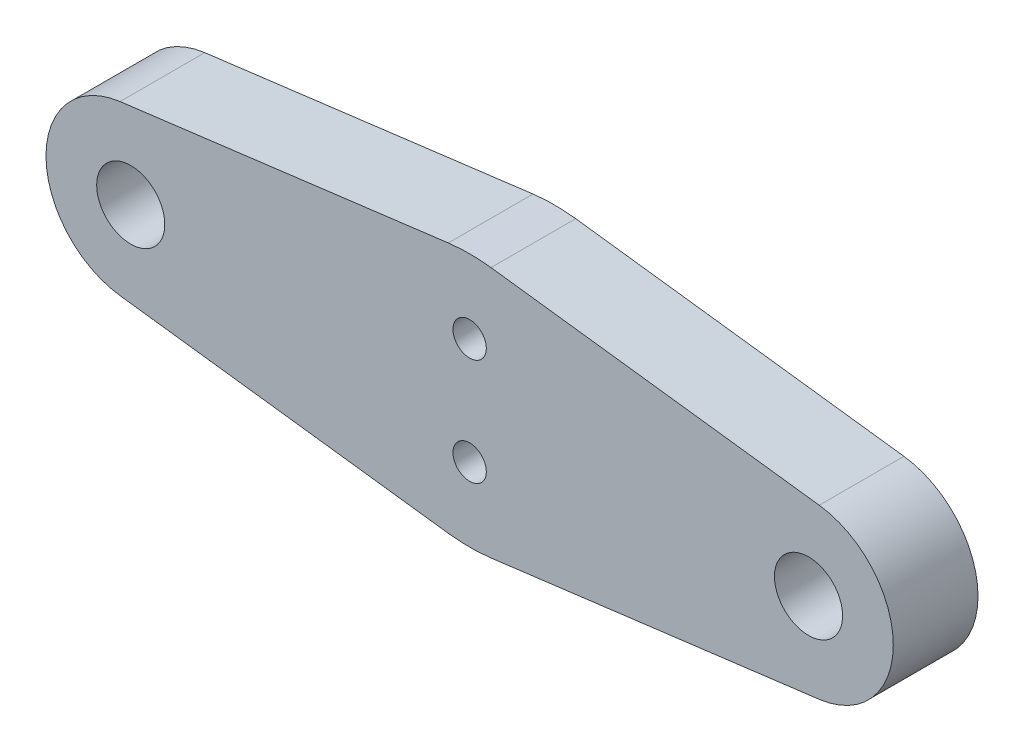
SolidWorks part; units mm, degrees
material "6061-T6 (SS)"
ref_plane "Front" through (0, 0, 0) normal (0, 0, 1) x (1, 0, 0)
ref_plane "Top" through (0, 0, 0) normal (0, 1, 0) x (1, 0, 0)
ref_plane "Right" through (0, 0, 0) normal (1, 0, 0) x (0, 0, -1)
sketch "Sketch1" plane through (0, 0, 0) normal (0, 0, 1) x (1, 0, 0)
  line L0 (1.6002, 9.4238) -> (26.2001, 6.2994)
  line L5 (26.2001, -6.2994) -> (1.6002, -9.4238)
  line L6 (-1.6002, 9.4238) -> (-26.2001, 6.2994)
  line L7 (-26.2001, -6.2994) -> (-1.6002, -9.4238)
  line L8 (25.4, 0) -> (-25.4, 0) construction
  line L9 (0, 3.175) -> (0, -3.175) construction
  arc A1 (26.2001, 6.2994) -> (26.2001, -6.2994) centre (25.4, 0) cw
  arc A2 (-26.2001, 6.2994) -> (-26.2001, -6.2994) centre (-25.4, 0) ccw
  arc A3 (1.6002, 9.4238) -> (-1.6002, 9.4238) centre (0, -3.175) ccw
  arc A4 (1.6002, -9.4238) -> (-1.6002, -9.4238) centre (0, 3.175) cw
  dimension "D1" = 12.7
  dimension "D2" = 6.35
  dimension "D4" = 19.05
  dimension "D3" = 50.8
extrude "Boss-Extrude1" add sketch "Sketch1" along normal blind 6.35
sketch "Sketch4" plane through (0, 0, 0) normal (0, 0, -1) x (-1, 0, 0)
  line L0 (0, 4) -> (0, -4) construction
  point P0 (0, 4)
  point P2 (0, -4)
  dimension "D1" = 8
hole_wizard "M3x0.5 Tapped Hole1" positions "Sketch4" profile "Sketch3" tap size "M3x0.5" standard "ANSI Metric" end condition up to next
sketch "Sketch3" plane through (0, 4, 0) normal (1, 0, 0) x (0, 1, 0)
  line L0 (0, 0) -> (0, 6.35)
  line L1 (0, 6.35) -> (1.25, 6.35)
  line L2 (1.25, 6.35) -> (1.25, 0)
  line L5 (1.25, 0) -> (0, 0)
  line L11 (0, -6.35) -> (0, 107.95) construction
  dimension "Thru Tap Drill Dia." = 2.5
  dimension "Thru Tap Drill Depth" = 6.35
cosmetic thread "Hole Thread1" parameters "D2"=3
cosmetic thread "Hole Thread2" parameters "D2"=3
sketch "Sketch7" plane through (0, 0, 0) normal (0, 0, -1) x (-1, 0, 0)
  point P11 (25.4, 0)
  point P14 (-25.4, 0)
hole_wizard "#10 Clearance Hole1" positions "Sketch7" profile "Sketch6" hole size "#10" standard "ANSI Inch" end condition through all
sketch "Sketch6" plane through (-25.4, 0, 0) normal (1, 0, 0) x (0, 1, 0)
  line L0 (0, 0) -> (0, 6.35)
  line L1 (0, 6.35) -> (2.5527, 6.35)
  line L2 (2.5527, 6.35) -> (2.5527, 0)
  line L5 (2.5527, 0) -> (0, 0)
  line L11 (0, -6.35) -> (0, 107.95) construction
  dimension "Thru Hole Dia." = 5.1054
  dimension "Thru Hole Depth" = 6.35
